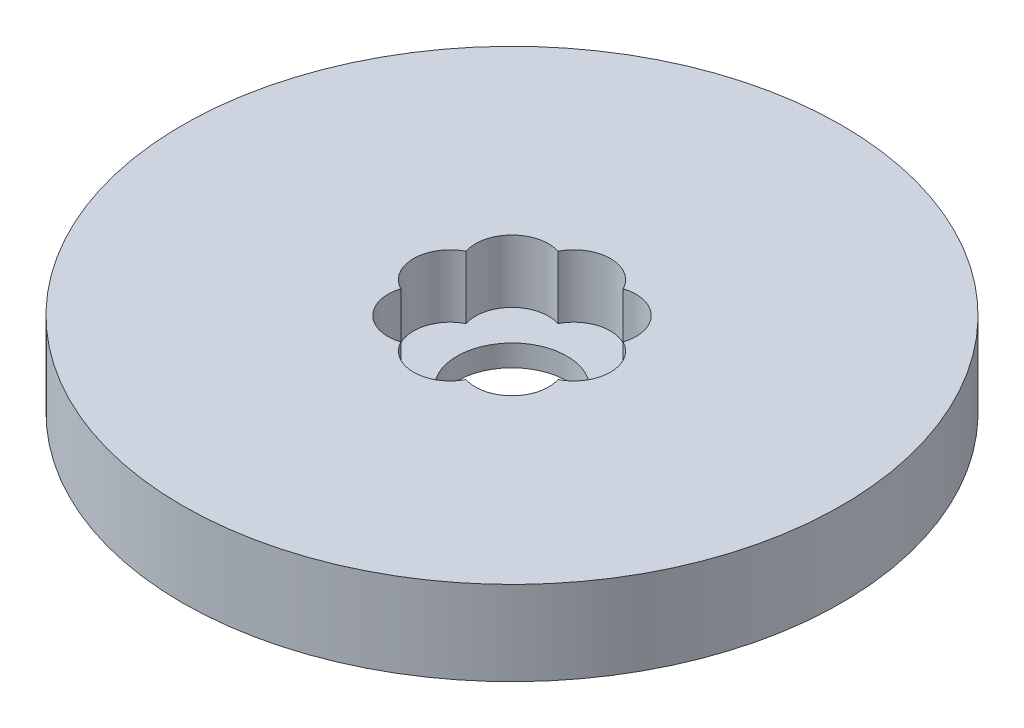
SolidWorks part; units mm, degrees
ref_plane "Front Plane" through (0, 0, 0) normal (0, 0, 1) x (1, 0, 0)
ref_plane "Top Plane" through (0, 0, 0) normal (0, 1, 0) x (1, 0, 0)
ref_plane "Right Plane" through (0, 0, 0) normal (1, 0, 0) x (0, 0, -1)
sketch "Sketch1" plane through (0, 0, 0) normal (0, 1, 0) x (1, 0, 0)
  circle A0 centre (0, 0) radius 90
  dimension "FLANGE_OD" = 180
extrude "Boss-Extrude1" add sketch "Sketch1" along normal blind 23
sketch "Sketch2" plane through (0, 0, 0) normal (0, 1, 0) x (1, 0, 0)
  circle A0 centre (0, 0) radius 15
  dimension "BORE_D" = 30
extrude "Cut-Extrude1" cut sketch "Sketch2" along normal through all
sketch "Sketch3" plane through (0, 23, 0) normal (0, 1, 0) x (1, 0, 0)
  circle A0 centre (0, 0) radius 16.8898 construction
  circle A1 centre (-16.8898, 0) radius 10
  dimension "BOLT_D" = 20
  dimension "BOLT_PCD" = 33.7796
extrude "Cut-Extrude2" cut sketch "Sketch3" against normal blind 17.1267
pattern_circular "CirPattern1" count 8 over 360 about axis through (0, 0, 0) along (0, 1, 0) of "Cut-Extrude2"
